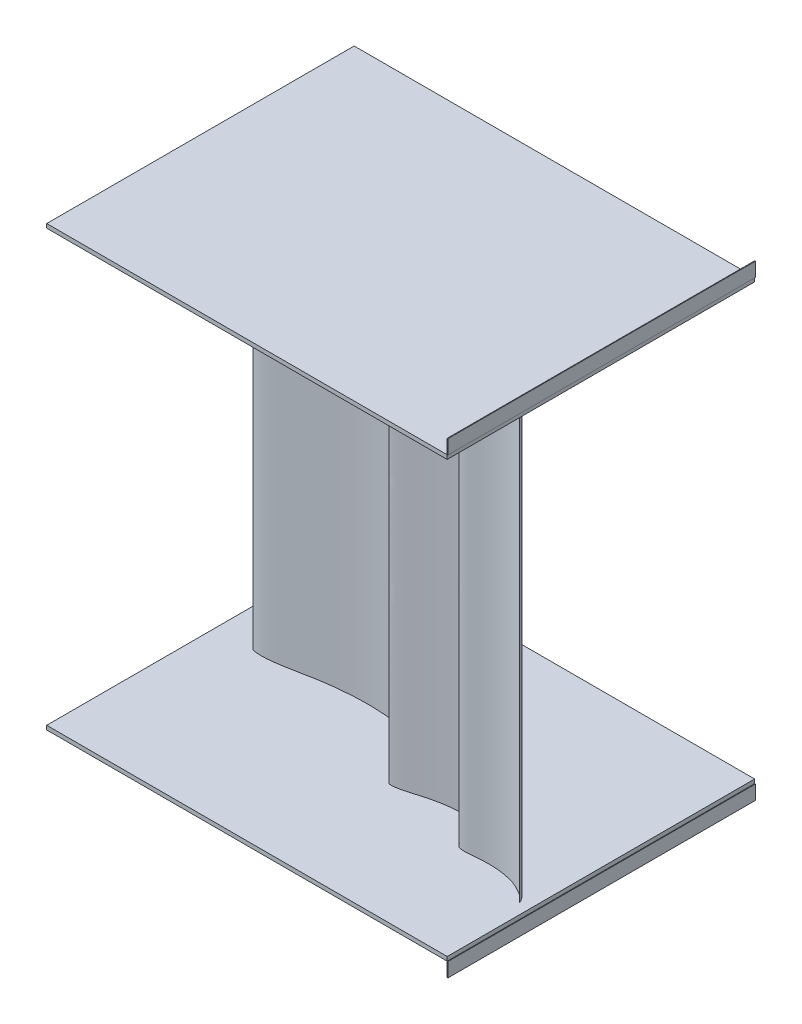
SolidWorks part; units mm, degrees
ref_plane "Front Plane" through (0, 0, 0) normal (0, 0, 1) x (1, 0, 0)
ref_plane "Top Plane" through (0, 0, 0) normal (0, 1, 0) x (1, 0, 0)
ref_plane "Right Plane" through (0, 0, 0) normal (1, 0, 0) x (0, 0, -1)
ref_plane "Plane3" through (0, -431.165, 0) normal (0, 1, 0) x (1, 0, 0)
sketch "Sketch7" plane through (0, -431.165, 0) normal (0, 1, 0) x (1, 0, 0)
  line L3 (2028.85, -589.13) -> (1241.45, -589.13)
  line L6 (1241.45, -1193.65) -> (1241.45, -589.13)
  line L8 (2028.85, -1193.65) -> (2028.85, -589.13)
  line L9 (2028.85, -1193.65) -> (1241.45, -1193.65)
  dimension "D1" = 2028.85
  dimension "D2" = 1193.65
  dimension "D3" = 787.4
  dimension "D4" = 604.52
sketch "Sketch8" plane through (0, 0, 0) normal (0, 1, 0) x (1, 0, 0)
  line L0 (1896.0126, -962.7836) -> (1676.2236, -953.149) construction
  line L1 (1314.0753, -855) -> (1734.7302, -915.6173) construction
  line L2 (1734.7302, -915.6173) -> (1676.2236, -953.149) construction
  line L4 (1314.0753, -855) -> (1319.04, -824.8801) construction
  line L5 (2008.9265, -1031.5984) -> (1853.6118, -993.1619) construction
  line L6 (1734.7302, -915.6173) -> (2013.3954, -915.6173) construction
  line L7 (1853.6118, -993.1619) -> (1896.0126, -962.7836) construction
  line L8 (1896.0126, -962.7836) -> (2113.872, -962.7836) construction
  line L9 (1896.0126, -962.7836) -> (1611.1884, -962.7836) construction
  line L10 (2008.9265, -1031.5984) -> (1908.4474, -1031.5984) construction
  line L16 (2028.85, -589.13) -> (1241.45, -589.13)
  line L17 (1241.45, -589.13) -> (1241.45, -1193.65)
  line L18 (1241.45, -1193.65) -> (2028.85, -1193.65)
  line L19 (2028.85, -1193.65) -> (2028.85, -589.13)
  line L20 (2028.85, -589.13) -> (1241.45, -589.13)
  line L21 (1241.45, -589.13) -> (1241.45, -1193.65)
  line L22 (1241.45, -1193.65) -> (2028.85, -1193.65)
  line L23 (2028.85, -1193.65) -> (2028.85, -589.13)
  spline S2 degree 3 poles (1896.0126, -962.7836) (1895.4061, -961.9813) (1894.5256, -960.8164) (1893.0202, -959.4736) (1891.9514, -958.5728) (1890.9835, -957.615) (1889.9301, -956.8753) (1888.8272, -956.0613) (1887.5489, -955.2375) (1886.2825, -954.2949) (1884.7233, -953.5914) (1883.2352, -952.6696) (1881.6303, -951.8822) (1879.9731, -951.0584) (1878.2946, -950.3229) (1876.6403, -949.5478) (1875.0645, -948.8012) (1873.4398, -948.068) (1871.755, -947.3306) (1870.0069, -946.5947) (1868.2088, -945.8326) (1866.3229, -945.0828) (1864.3352, -944.3316) (1862.2467, -943.5757) (1860.0434, -942.794) (1857.7237, -942.0554) (1855.3392, -941.2719) (1852.8936, -940.5088) (1850.3907, -939.8336) (1847.876, -939.1665) (1845.3582, -938.5369) (1842.8407, -937.9426) (1840.316, -937.4205) (1837.7875, -936.9667) (1835.2619, -936.5383) (1832.7245, -936.2297) (1830.1967, -935.8763) (1827.6616, -935.5985) (1825.123, -935.3793) (1822.5852, -935.1786) (1820.0472, -934.9783) (1817.5053, -934.8632) (1814.9635, -934.7367) (1812.4197, -934.6891) (1809.8765, -934.575) (1807.3296, -934.5687) (1804.781, -934.5931) (1802.2315, -934.6374) (1799.6815, -934.7163) (1797.1308, -934.8095) (1794.5762, -934.889) (1792.0237, -935.0622) (1789.4686, -935.2296) (1786.9096, -935.3927) (1784.3549, -935.6457) (1781.7956, -935.8847) (1779.2318, -936.1302) (1776.6771, -936.484) (1774.1105, -936.7763) (1771.5498, -937.1309) (1768.9836, -937.481) (1766.419, -937.8808) (1763.8523, -938.3091) (1761.2836, -938.7586) (1758.7157, -939.2375) (1756.146, -939.7242) (1753.5903, -940.214) (1751.0656, -940.7832) (1748.5702, -941.3218) (1746.1409, -941.8827) (1743.7872, -942.4259) (1741.5193, -942.9937) (1739.308, -943.5593) (1737.14, -944.1433) (1735.0148, -944.7332) (1732.9199, -945.2861) (1730.891, -945.8607) (1728.9113, -946.4673) (1726.9362, -947.0251) (1724.9914, -947.6136) (1723.0656, -948.2015) (1721.1627, -948.7848) (1719.2274, -949.3326) (1717.2882, -949.9347) (1715.314, -950.5014) (1713.3524, -951.1023) (1711.3803, -951.666) (1709.3957, -952.2526) (1707.3662, -952.8277) (1705.2799, -953.413) (1703.1128, -953.991) (1700.8596, -954.5335) (1698.515, -955.0979) (1696.0607, -955.6034) (1693.534, -956.1045) (1690.9669, -956.5434) (1688.4055, -956.9069) (1685.8421, -957.1294) (1683.2939, -957.2548) (1680.7218, -957.2613) (1678.7711, -957.0514) (1677.1971, -956.861) (1676.6577, -955.9944) (1676.134, -954.8182) (1676.1872, -953.8284) (1676.2236, -953.149) knots 0 0 0 0 0.01297 0.01883 0.026053 0.031073 0.036412 0.042675 0.048819 0.056099 0.063029 0.070869 0.078731 0.08615 0.094825 0.102443 0.109796 0.117394 0.125513 0.133599 0.141944 0.150791 0.159864 0.169447 0.179539 0.190121 0.200953 0.212027 0.223275 0.234503 0.245702 0.256866 0.267981 0.279066 0.290116 0.301131 0.312145 0.323151 0.334135 0.345124 0.356102 0.367084 0.378056 0.38904 0.400013 0.411002 0.421999 0.433003 0.444005 0.455021 0.46604 0.477082 0.48813 0.499184 0.510268 0.521355 0.532455 0.543599 0.554732 0.565889 0.577057 0.588256 0.599481 0.610738 0.622009 0.63329 0.644591 0.655686 0.666786 0.677634 0.687956 0.698051 0.707893 0.717499 0.727111 0.736441 0.745542 0.754403 0.76324 0.772104 0.780702 0.789303 0.797863 0.806734 0.815583 0.824447 0.833287 0.84213 0.851233 0.860589 0.870175 0.880262 0.890586 0.901386 0.912692 0.923927 0.93509 0.94617 0.957198 0.968178 0.979173 0.983282 0.9875 0.991419 1 1 1 1
  spline S3 degree 3 poles (1676.2236, -953.149) (1676.2485, -952.8231) (1676.2986, -952.1665) (1676.5132, -951.1878) (1676.8292, -950.2088) (1677.2564, -949.2276) (1677.7911, -948.2415) (1678.4334, -947.2483) (1679.1823, -946.2459) (1680.0373, -945.2329) (1680.9976, -944.2083) (1682.0622, -943.1717) (1683.2302, -942.1233) (1684.5005, -941.0638) (1685.872, -939.9946) (1687.3432, -938.9176) (1688.9126, -937.8352) (1690.5788, -936.7502) (1692.34, -935.666) (1694.1944, -934.5863) (1696.1401, -933.5149) (1698.175, -932.4562) (1700.297, -931.4143) (1703.2784, -930.0356) (1707.2082, -928.3836) (1712.1762, -926.5606) (1716.5172, -925.1906) (1721.0697, -923.9197) (1724.8413, -923.002) (1729.7024, -921.9798) (1734.7377, -921.0822) (1740.9363, -920.2154) (1746.2195, -919.6563) (1750.5259, -919.2953) (1753.8079, -919.0649) (1757.1216, -918.8736) (1760.4639, -918.719) (1763.8317, -918.5983) (1767.2218, -918.5092) (1770.6309, -918.4493) (1774.0558, -918.4165) (1777.4932, -918.4091) (1782.0918, -918.4313) (1786.6958, -918.4996) (1791.3004, -918.6125) (1794.7496, -918.7218) (1798.1912, -918.8506) (1801.6218, -919.023) (1805.0338, -919.3126) (1808.4245, -919.694) (1811.7906, -920.1649) (1815.1292, -920.7164) (1818.4374, -921.3408) (1821.7122, -922.0304) (1824.9509, -922.7775) (1828.1505, -923.5751) (1831.3081, -924.4169) (1834.4209, -925.297) (1837.486, -926.2109) (1840.5007, -927.1546) (1843.4619, -928.1252) (1846.3668, -929.1208) (1849.2127, -930.1403) (1851.9966, -931.1834) (1854.7157, -932.2504) (1857.3673, -933.3421) (1859.9487, -934.4596) (1862.4572, -935.6041) (1864.8901, -936.7767) (1867.2449, -937.9783) (1869.5193, -939.2092) (1871.7109, -940.4689) (1873.8174, -941.7562) (1875.8368, -943.0689) (1877.7671, -944.4035) (1879.6066, -945.7556) (1881.3535, -947.1194) (1883.0064, -948.4879) (1884.5639, -949.853) (1886.025, -951.2055) (1887.7972, -952.9341) (1889.7588, -954.9907) (1892.0165, -957.5704) (1893.7821, -959.7686) (1894.979, -961.3595) (1895.5192, -962.0976) (1895.7743, -962.4507) (1895.9274, -962.6643) (1895.9955, -962.7597) (1896.0126, -962.7836) knots 0 0 0 0 0.004018 0.008097 0.012294 0.016663 0.021247 0.026085 0.031207 0.036637 0.042391 0.048482 0.054918 0.061703 0.068836 0.076317 0.084139 0.092298 0.100784 0.10959 0.118704 0.128117 0.137818 0.147796 0.16854 0.190267 0.212906 0.224546 0.248433 0.260666 0.285677 0.311368 0.337682 0.351052 0.364552 0.378172 0.391902 0.40573 0.419646 0.433638 0.447693 0.461798 0.475942 0.504289 0.518466 0.532628 0.54676 0.560852 0.574898 0.588895 0.60284 0.616724 0.630537 0.64427 0.657909 0.67144 0.684851 0.698126 0.711251 0.724214 0.737001 0.749602 0.762006 0.774204 0.786189 0.797954 0.809494 0.820805 0.831885 0.84273 0.853339 0.863709 0.873837 0.883718 0.893347 0.902715 0.911811 0.920619 0.929121 0.937297 0.945119 0.959587 0.972264 0.987301 0.994278 0.996765 0.998557 0.999639 1 1 1 1
  spline S6 degree 3 poles (2008.9265, -1031.5984) (2008.6093, -1030.9393) (2008.1489, -1029.9823) (2007.2684, -1028.8088) (2006.6359, -1028.0131) (2006.0833, -1027.1912) (2005.4386, -1026.5125) (2004.7691, -1025.7738) (2003.9761, -1025.0028) (2003.2086, -1024.1489) (2002.198, -1023.4234) (2001.2695, -1022.5525) (2000.2384, -1021.7606) (1999.1752, -1020.9352) (1998.0842, -1020.1698) (1997.016, -1019.3796) (1995.9998, -1018.621) (1994.9468, -1017.8649) (1993.8515, -1017.0972) (1992.7109, -1016.3215) (1991.5384, -1015.5198) (1990.3016, -1014.7144) (1988.9923, -1013.8934) (1987.6119, -1013.0545) (1986.1533, -1012.1807) (1984.6055, -1011.321) (1983.0181, -1010.4199) (1981.3841, -1009.5246) (1979.6966, -1008.6837) (1977.9996, -1007.8469) (1976.2949, -1007.0365) (1974.5854, -1006.2512) (1972.8604, -1005.5163) (1971.1229, -1004.8296) (1969.3838, -1004.1614) (1967.6191, -1003.577) (1965.8677, -1002.962) (1964.1001, -1002.3998) (1962.3217, -1001.8789) (1960.5413, -1001.3714) (1958.7606, -1000.864) (1956.9649, -1000.4169) (1955.1709, -999.9616) (1953.3641, -999.5623) (1951.5673, -999.1157) (1949.7524, -998.7454) (1947.9319, -998.3968) (1946.1078, -998.0622) (1944.2785, -997.7522) (1942.4466, -997.4523) (1940.6138, -997.142) (1938.7692, -996.8989) (1936.9235, -996.6513) (1935.0756, -996.4001) (1933.2179, -996.2135) (1931.3589, -996.0163) (1929.4958, -995.8231) (1927.6236, -995.7084) (1925.7518, -995.5482) (1923.8752, -995.4332) (1921.9953, -995.3142) (1920.1095, -995.231) (1918.2181, -995.1676) (1916.3221, -995.1191) (1914.4226, -995.0918) (1912.5206, -995.0697) (1910.6282, -995.0519) (1908.7464, -995.0951) (1906.89, -995.1207) (1905.0774, -995.1716) (1903.3214, -995.2208) (1901.6229, -995.2999) (1899.9651, -995.3855) (1898.3356, -995.4906) (1896.7357, -995.6059) (1895.1627, -995.6992) (1893.6337, -995.8174) (1892.1351, -995.9656) (1890.6469, -996.0796) (1889.1758, -996.2198) (1887.7183, -996.3624) (1886.278, -996.505) (1884.8195, -996.6175) (1883.3505, -996.7682) (1881.8615, -996.8888) (1880.3767, -997.0354) (1878.8898, -997.1541) (1877.3906, -997.2872) (1875.861, -997.4058) (1874.2896, -997.5235) (1872.6615, -997.6242) (1870.9772, -997.6874) (1869.2246, -997.753) (1867.4022, -997.7609) (1865.5287, -997.7553) (1863.6355, -997.6995) (1861.7572, -997.5908) (1859.8976, -997.3812) (1858.0629, -997.1047) (1856.2282, -996.7399) (1854.8676, -996.3101) (1853.7727, -995.9482) (1853.5126, -995.2529) (1853.3082, -994.3391) (1853.4883, -993.6411) (1853.6118, -993.1619) knots 0 0 0 0 0.01297 0.01883 0.026053 0.031073 0.036412 0.042675 0.048819 0.056099 0.063029 0.070869 0.078731 0.08615 0.094825 0.102443 0.109796 0.117394 0.125513 0.133599 0.141944 0.150791 0.159864 0.169447 0.179539 0.190121 0.200953 0.212027 0.223275 0.234503 0.245702 0.256866 0.267981 0.279066 0.290116 0.301131 0.312145 0.323151 0.334135 0.345124 0.356102 0.367084 0.378056 0.38904 0.400013 0.411002 0.421999 0.433003 0.444005 0.455021 0.46604 0.477082 0.48813 0.499184 0.510268 0.521355 0.532455 0.543599 0.554732 0.565889 0.577057 0.588256 0.599481 0.610738 0.622009 0.63329 0.644591 0.655686 0.666786 0.677634 0.687956 0.698051 0.707893 0.717499 0.727111 0.736441 0.745542 0.754403 0.76324 0.772104 0.780702 0.789303 0.797863 0.806734 0.815583 0.824447 0.833287 0.84213 0.851233 0.860589 0.870175 0.880262 0.890586 0.901386 0.912692 0.923927 0.93509 0.94617 0.957198 0.968178 0.979173 0.983282 0.9875 0.991419 1 1 1 1
  spline S7 degree 3 poles (1853.6118, -993.1619) (1853.6764, -992.9332) (1853.8064, -992.4722) (1854.1, -991.8053) (1854.4659, -991.1527) (1854.9113, -990.5145) (1855.4342, -989.8883) (1856.0348, -989.2724) (1856.7127, -988.6653) (1857.4678, -988.0659) (1858.2995, -987.4734) (1859.2074, -986.8872) (1860.1908, -986.3075) (1861.2486, -985.7346) (1862.3799, -985.1693) (1863.5835, -984.6127) (1864.8579, -984.0664) (1866.2017, -983.5322) (1867.613, -983.0122) (1869.0902, -982.5087) (1870.6312, -982.0244) (1872.2341, -981.5618) (1873.8966, -981.1238) (1876.2202, -980.569) (1879.2592, -979.9557) (1883.063, -979.3695) (1886.3547, -979.0162) (1889.7829, -978.764) (1892.6037, -978.6514) (1896.2162, -978.6208) (1899.9351, -978.7041) (1904.4789, -978.9764) (1908.3258, -979.3366) (1911.4479, -979.6978) (1913.8208, -980.0048) (1916.2108, -980.3444) (1918.616, -980.7142) (1921.0344, -981.1119) (1923.4641, -981.5353) (1925.9033, -981.9822) (1928.3497, -982.4507) (1930.8015, -982.9391) (1934.0769, -983.6154) (1937.3495, -984.3254) (1940.6161, -985.0673) (1943.0596, -985.6405) (1945.4947, -986.2267) (1947.9158, -986.8423) (1950.3068, -987.5389) (1952.6694, -988.2978) (1955.0016, -989.117) (1957.3027, -989.9896) (1959.5716, -990.91) (1961.8073, -991.8719) (1964.009, -992.8697) (1966.1756, -993.898) (1968.3059, -994.9516) (1970.3988, -996.0262) (1972.4528, -997.118) (1974.4665, -998.2238) (1976.4383, -999.3411) (1978.3664, -1000.4681) (1980.2489, -1001.6037) (1982.0839, -1002.7472) (1983.8693, -1003.8985) (1985.603, -1005.0576) (1987.2828, -1006.2251) (1988.9069, -1007.4014) (1990.473, -1008.5868) (1991.9793, -1009.7817) (1993.424, -1010.9859) (1994.8056, -1012.1988) (1996.1225, -1013.4192) (1997.3737, -1014.6451) (1998.5583, -1015.8738) (1999.6755, -1017.102) (2000.7251, -1018.3252) (2001.707, -1019.5383) (2002.6214, -1020.7352) (2003.4687, -1021.9093) (2004.484, -1023.3963) (2005.5871, -1025.1443) (2006.8262, -1027.3078) (2007.7693, -1029.1285) (2008.3941, -1030.4347) (2008.6732, -1031.0385) (2008.8044, -1031.3268) (2008.8829, -1031.5011) (2008.9178, -1031.5789) (2008.9265, -1031.5984) knots 0 0 0 0 0.004018 0.008097 0.012294 0.016663 0.021247 0.026085 0.031207 0.036637 0.042391 0.048482 0.054918 0.061703 0.068836 0.076317 0.084139 0.092298 0.100784 0.10959 0.118704 0.128117 0.137818 0.147796 0.16854 0.190267 0.212906 0.224546 0.248433 0.260666 0.285677 0.311368 0.337682 0.351052 0.364552 0.378172 0.391902 0.40573 0.419646 0.433638 0.447693 0.461798 0.475942 0.504289 0.518466 0.532628 0.54676 0.560852 0.574898 0.588895 0.60284 0.616724 0.630537 0.64427 0.657909 0.67144 0.684851 0.698126 0.711251 0.724214 0.737001 0.749602 0.762006 0.774204 0.786189 0.797954 0.809494 0.820805 0.831885 0.84273 0.853339 0.863709 0.873837 0.883718 0.893347 0.902715 0.911811 0.920619 0.929121 0.937297 0.945119 0.959587 0.972264 0.987301 0.994278 0.996765 0.998557 0.999639 1 1 1 1
  spline S8 degree 3 poles (1314.0753, -855) (1314.0825, -855.1181) (1314.1612, -856.3968) (1313.5566, -858.3073) (1314.3777, -860.552) (1315.2322, -862.3223) (1318.2275, -862.9894) (1321.9335, -863.7667) (1326.8802, -864.2468) (1331.8023, -864.4937) (1336.7727, -864.5571) (1341.766, -864.3489) (1346.7848, -863.9968) (1351.738, -863.5175) (1356.5527, -863.0158) (1361.1677, -862.3801) (1366.9863, -861.578) (1372.5937, -860.5989) (1378.0135, -859.6304) (1381.941, -858.8828) (1385.8399, -858.177) (1389.7257, -857.3977) (1393.6293, -856.6863) (1397.4724, -855.9004) (1401.2976, -855.218) (1405.0671, -854.4612) (1408.8817, -853.6999) (1412.7329, -852.9411) (1416.6364, -852.2471) (1420.5582, -851.4602) (1424.5685, -850.7443) (1428.7013, -850.0828) (1432.8997, -849.3559) (1437.179, -848.6484) (1441.5381, -847.9848) (1446.0065, -847.3275) (1450.635, -846.7342) (1455.4123, -846.1214) (1460.3124, -845.564) (1465.2747, -844.9534) (1470.2813, -844.5013) (1475.3143, -844.0578) (1480.3421, -843.629) (1485.3662, -843.257) (1490.3822, -842.9254) (1495.3886, -842.6479) (1500.3888, -842.4665) (1505.379, -842.2754) (1510.3688, -842.2049) (1515.3474, -842.0142) (1520.3229, -842.0334) (1525.2884, -842.064) (1530.2478, -842.0671) (1535.1982, -842.2436) (1540.1419, -842.4112) (1545.0817, -842.5672) (1550.0077, -842.9036) (1554.9287, -843.213) (1559.8457, -843.5498) (1564.7551, -843.9529) (1569.6589, -844.3941) (1574.5537, -844.894) (1579.4206, -845.6004) (1584.3015, -846.1793) (1589.1634, -846.9092) (1594.0276, -847.6174) (1598.868, -848.4886) (1603.7079, -849.3604) (1608.5458, -850.268) (1613.3659, -851.2875) (1618.1574, -852.451) (1622.976, -853.5301) (1627.7489, -854.8374) (1632.5224, -856.194) (1637.2757, -857.6814) (1642.0012, -859.306) (1646.7207, -860.9984) (1651.4269, -862.7624) (1657.6206, -865.1135) (1663.58, -867.7829) (1669.4152, -870.3019) (1673.5009, -872.2267) (1678.5617, -874.65) (1683.3412, -877.0575) (1687.8401, -879.5165) (1691.0596, -881.266) (1694.157, -883.0061) (1697.1397, -884.7268) (1700.0259, -886.4637) (1703.0576, -888.2705) (1706.1432, -890.0058) (1709.1711, -891.9069) (1712.1054, -893.7279) (1714.7894, -895.7848) (1717.6519, -897.4358) (1719.9057, -899.4904) (1722.2052, -901.3189) (1724.1695, -903.0948) (1726.0527, -904.7185) (1727.7299, -906.745) (1729.6118, -908.6814) (1732.2486, -911.5508) (1733.718, -913.9588) (1734.7302, -915.6173) knots 0 0 0 0 0.000793 0.008585 0.012504 0.016722 0.020831 0.031826 0.042806 0.053834 0.064914 0.076077 0.087312 0.098618 0.109417 0.119742 0.129829 0.14877 0.157874 0.166717 0.175556 0.184421 0.19327 0.20214 0.210701 0.219301 0.227899 0.236764 0.2456 0.254461 0.263562 0.272892 0.282504 0.29211 0.301952 0.312047 0.322369 0.333217 0.344317 0.355411 0.366713 0.377994 0.389264 0.400521 0.411747 0.422945 0.434114 0.44527 0.456404 0.467547 0.478647 0.489735 0.500818 0.511872 0.52292 0.533962 0.544981 0.555997 0.566999 0.578002 0.589 0.599989 0.610962 0.621945 0.632918 0.6439 0.654877 0.665866 0.67685 0.687856 0.69887 0.709885 0.720935 0.73202 0.743135 0.754299 0.765498 0.776726 0.787974 0.80988 0.820462 0.830554 0.840136 0.858057 0.866402 0.874487 0.882606 0.890205 0.897557 0.905175 0.913851 0.921269 0.929131 0.936971 0.943902 0.951181 0.957325 0.963588 0.968927 0.973947 0.98117 0.98703 1 1 1 1
  spline S9 degree 3 poles (1734.7302, -915.6173) (1734.0423, -913.9615) (1732.9859, -911.4188) (1731.1115, -908.1687) (1729.209, -905.744) (1727.2219, -903.2786) (1724.865, -901.1935) (1722.6538, -899.0731) (1720.2391, -897.1403) (1717.7532, -895.1235) (1715.3016, -893.1772) (1713.008, -891.4139) (1710.8413, -889.8239) (1708.6843, -888.1588) (1706.2487, -886.5921) (1703.7846, -884.8639) (1701.214, -883.1783) (1698.5834, -881.3744) (1695.8391, -879.6078) (1693.0863, -877.8922) (1690.3533, -876.1731) (1687.5429, -874.5168) (1683.7591, -872.2114) (1679.8686, -869.9422) (1675.8725, -867.6393) (1672.6849, -865.9084) (1669.4107, -864.1055) (1666.0245, -862.3485) (1662.6533, -860.503) (1659.1356, -858.7781) (1655.5576, -856.9329) (1651.7998, -855.0951) (1647.944, -853.2097) (1643.9554, -851.3507) (1639.8056, -849.4843) (1635.5555, -847.5652) (1631.1974, -845.609) (1626.7381, -843.7067) (1622.206, -841.7932) (1617.626, -839.8183) (1612.9397, -838.0271) (1608.2517, -836.1687) (1603.5497, -834.3688) (1597.2471, -832.0939) (1590.9871, -829.7334) (1584.6817, -827.5313) (1579.9301, -826.0059) (1575.1827, -824.4949) (1570.4268, -823.008) (1564.1436, -820.8839) (1557.7603, -819.1052) (1551.4106, -817.2623) (1546.6301, -815.9735) (1541.8339, -814.7692) (1537.0487, -813.5375) (1532.2542, -812.359) (1527.4587, -811.1976) (1522.6434, -810.1417) (1517.8241, -809.1248) (1513.0045, -808.123) (1508.1671, -807.225) (1503.3311, -806.3257) (1498.4796, -805.5287) (1493.6099, -804.8543) (1488.7453, -804.142) (1483.8629, -803.5592) (1478.9785, -802.9759) (1474.0766, -802.5434) (1469.177, -802.0637) (1464.2669, -801.671) (1459.3489, -801.333) (1454.4211, -801.0406) (1449.482, -800.8387) (1444.5322, -800.7092) (1439.572, -800.654) (1434.6008, -800.6582) (1429.6224, -800.7796) (1424.6263, -800.8521) (1419.6257, -801.182) (1414.6019, -801.4878) (1409.5683, -801.9385) (1404.5993, -802.4753) (1399.8199, -803.0943) (1395.3864, -803.731) (1391.2954, -804.4001) (1387.492, -805.1985) (1383.8529, -805.937) (1379.3955, -807.0558) (1375.1617, -808.1701) (1371.1779, -809.3546) (1368.3607, -810.256) (1365.6681, -811.2186) (1363.0442, -812.1767) (1360.4883, -813.1339) (1358.011, -814.1316) (1355.6065, -815.1809) (1353.293, -816.3002) (1351.0295, -817.3912) (1348.8946, -818.4942) (1346.9493, -819.5877) (1345.0302, -820.5889) (1343.1845, -821.6846) (1341.4102, -822.7907) (1339.738, -823.8699) (1338.2047, -825.0091) (1336.5642, -826.058) (1335.0246, -827.2714) (1333.4063, -828.3977) (1331.9835, -829.6592) (1330.5579, -830.8332) (1329.2128, -832.0628) (1327.8187, -833.3268) (1326.4907, -834.6657) (1324.8288, -836.4161) (1323.3181, -838.2033) (1321.7939, -839.8966) (1320.8084, -841.1927) (1319.8298, -842.4845) (1318.9582, -843.904) (1318.021, -845.3658) (1317.1932, -847.0077) (1316.2454, -848.6318) (1315.4123, -850.3821) (1314.5929, -852.1048) (1314.3596, -853.7073) (1314.1505, -854.6578) (1314.0753, -855) knots 0 0 0 0 0.011426 0.017546 0.023852 0.031067 0.037693 0.043881 0.050605 0.057403 0.064303 0.070569 0.075854 0.081445 0.087939 0.094312 0.100641 0.107544 0.114656 0.121456 0.128233 0.135247 0.142261 0.156493 0.163973 0.171676 0.179627 0.187813 0.196007 0.204136 0.212797 0.221684 0.230817 0.240172 0.249749 0.259839 0.269916 0.280217 0.290759 0.301294 0.312025 0.322753 0.33346 0.344135 0.36549 0.37613 0.38673 0.397318 0.407907 0.418511 0.439617 0.450159 0.46068 0.471194 0.481699 0.492196 0.502685 0.513169 0.523637 0.5341 0.544565 0.555017 0.565473 0.575919 0.586373 0.59683 0.607279 0.617746 0.628214 0.638679 0.649162 0.659655 0.670164 0.68069 0.691235 0.701802 0.712395 0.722998 0.733664 0.744352 0.7551 0.765894 0.776228 0.785837 0.794461 0.802661 0.810622 0.818143 0.831966 0.838544 0.84465 0.85083 0.856781 0.862467 0.868237 0.873813 0.879196 0.884627 0.88984 0.894519 0.898859 0.903643 0.908203 0.912197 0.916332 0.920381 0.924604 0.928828 0.932943 0.936719 0.940607 0.944563 0.94872 0.952631 0.959956 0.963643 0.967152 0.970338 0.973973 0.977769 0.981405 0.985692 0.989749 0.993788 0.997763 1 1 1 1
  dimension "D1" = 144.38
  dimension "D2" = 220
  dimension "D3" = 52.16
  dimension "D4" = 13.9
  dimension "D5" = 160
  dimension "D6" = 147.32
  dimension "D7" = 2.51
  dimension "D8" = 69.51
  dimension "D9" = 0
extrude "Boss-Extrude10" add sketch "Sketch7" along normal blind 8
sketch "Sketch10" plane through (0, -431.165, 0) normal (0, 1, 0) x (1, 0, 0)
  line L0 (2028.85, -1193.65) -> (2028.85, -589.13)
extrude "Extrude-Thin1" add sketch "Sketch10" against normal blind 28 thin thin type one direction wall 1.27
sketch3d "3DSketch1"
  spline S6 degree 3 poles (942.5392, 188.4893, 77.3735) (942.832, 206.2376, 89.8009) (943.1316, 224.3948, 102.5148) (943.4379, 242.961, 115.515) (943.4592, 244.157, 116.4183) (943.4737, 244.9459, 117.0306) (943.481, 245.3372, 117.3406) (943.8045, 262.6762, 131.0729) (944.2671, 272.861, 150.7043) (944.7874, 274.1067, 172.7831) (944.7986, 274.1335, 173.2594) (944.8211, 274.1783, 174.2126) (944.8548, 274.2277, 175.644) (947.8227, 274.2277, 301.5982) (950.7912, 274.2277, 427.5757) (953.7602, 274.2277, 553.5766) (953.7955, 274.2114, 555.0778) (953.8191, 274.1966, 556.0786) (953.8309, 274.1877, 556.5789) (954.4859, 273.6948, 584.3754) (955.1304, 268.6853, 611.729) (955.7473, 259.2854, 637.9089) (955.771, 258.9244, 638.9142) (955.8183, 258.1899, 640.9201) (955.889, 257.0625, 643.9205) (958.5742, 211.2068, 757.88) (961.2452, 165.5959, 871.2312) (963.9018, 120.2297, 983.9742) (963.9285, 119.7336, 985.1083) (963.9462, 119.3949, 985.8605) (963.9551, 119.2225, 986.2351) (964.5802, 107.0139, 1012.7657) (964.9651, 82.8061, 1029.1002) (964.998, 53.6375, 1030.4941) (964.9984, 53.2336, 1030.5134) (964.9992, 52.4257, 1030.5456) (965, 51.2128, 1030.581) (965, 17.0709, 1030.581) (965, -17.0709, 1030.581) (965, -51.2128, 1030.581) (964.9992, -52.4257, 1030.5456) (964.9984, -53.2336, 1030.5134) (964.998, -53.6375, 1030.4941) (964.9651, -82.8061, 1029.1002) (964.5802, -107.0139, 1012.7657) (963.9551, -119.2225, 986.2351) (963.9462, -119.3949, 985.8605) (963.9285, -119.7336, 985.1083) (963.9018, -120.2297, 983.9742) (961.2452, -165.5959, 871.2312) (958.5742, -211.2068, 757.88) (955.889, -257.0625, 643.9205) (955.8183, -258.1899, 640.9201) (955.771, -258.9244, 638.9142) (955.7473, -259.2854, 637.9089) (955.1304, -268.6853, 611.729) (954.4859, -273.6948, 584.3754) (953.8309, -274.1877, 556.5789) (953.8191, -274.1966, 556.0786) (953.7955, -274.2114, 555.0778) (953.7602, -274.2277, 553.5766) (950.7912, -274.2277, 427.5757) (947.8227, -274.2277, 301.5982) (944.8548, -274.2277, 175.644) (944.8211, -274.1783, 174.2126) (944.7986, -274.1335, 173.2594) (944.7874, -274.1067, 172.7831) (944.2627, -272.8505, 150.5184) (943.7972, -262.5143, 130.7622) (943.4738, -244.9486, 117.0348) (943.4614, -244.2771, 116.5101) (943.4372, -242.9166, 115.4831) (943.4026, -240.8209, 114.0165) (943.1017, -222.679, 101.3134) (942.8124, -205.2351, 89.099) (942.5347, -188.4893, 77.3735) knots 0 0 0 0 0.029375 0.030052 0.030729 0.031406 0.031406 0.031406 0.059643 0.059643 0.059643 0.06029 0.060937 0.061584 0.231154 0.231833 0.232512 0.233191 0.233191 0.233191 0.270549 0.270549 0.270549 0.271995 0.273442 0.274888 0.438359 0.438917 0.439476 0.440034 0.440034 0.440034 0.475757 0.475757 0.475757 0.476305 0.476853 0.4774 0.522556 0.523104 0.523651 0.524199 0.524199 0.524199 0.559922 0.559922 0.559922 0.560481 0.561039 0.561598 0.725068 0.726515 0.727961 0.729408 0.729408 0.729408 0.766766 0.766766 0.766766 0.767444 0.768123 0.768802 0.938372 0.939019 0.939667 0.940314 0.940314 0.940314 0.968774 0.968774 0.968774 0.969931 0.971088 0.972245 1 1 1 1 weights 1 1 1 1 1 1 1 0.941603 0.94179 1.000561 1.000561 1.000561 1.000561 1.000561 1.000561 1.000561 1.000561 1.000561 1.000561 0.991124 0.990575 0.998913 0.998913 0.998913 0.998913 0.998913 0.998913 0.998913 0.998913 0.998913 0.998913 0.902209 0.902299 0.999183 0.999183 0.999183 0.999183 0.999183 0.999183 0.999183 0.999183 0.999183 0.999183 0.902299 0.902209 0.998913 0.998913 0.998913 0.998913 0.998913 0.998913 0.998913 0.998913 0.998913 0.998913 0.990575 0.991124 1.000561 1.000561 1.000561 1.000561 1.000561 1.000561 1.000561 1.000561 1.000561 1.000561 0.941325 0.941604 1.001399 1.001399 1.001399 1.001399 1.001399 1.001399 1.001399
sketch "Sketch12" plane through (0, 0, 0) normal (0, 1, 0) x (1, 0, 0)
  line L0 (1199.061, -595.1441) -> (1199.061, -643.2623) construction
  line L1 (967.5392, -77.3735) -> (967.5392, -1304.4116) construction
  line L2 (1040, -595.1441) -> (1238.0413, -595.1441)
  line L3 (1040, -595.1441) -> (1238.0413, -595.1441) construction
  line L4 (967.5392, -77.3735) -> (1085.2537, -1036.0813)
  line L5 (1077.558, -920.178) -> (1229.1053, -920.178) construction
  line L6 (1199.061, -595.1441) -> (1078.6209, -877.964)
  line L8 (990, -1043.281) -> (933.768, -1043.281) construction
  line L9 (1223.2734, -573.2347) -> (1261.1883, -569.4837) construction
  line L11 (-11.7203, -883.6813) -> (49988.2797, -883.6813) construction
  line L12 (990, -1030.581) -> (1083.706, -1023.4759)
  line L13 (1079.3229, -883.6813) -> (1211.0114, -574.4478)
  line L14 (990, -1043.281) -> (1085.2537, -1036.0813)
  line L15 (990, -1017.881) -> (1082.161, -1010.8931)
  line L16 (1083.706, -1023.4759) -> (1120.5127, -1020.6851)
  line L17 (1096.3696, -1022.5157) -> (979.7131, -72.4247)
  line L19 (1071.0423, -1024.4361) -> (955.1011, -80.1702)
  line L20 (1075.5317, -852.8043) -> (1185.2574, -595.1441)
  line L21 (1078.6209, -877.964) -> (1068.6999, -901.2609)
  line L23 (1081.8109, -877.839) -> (1101.7146, -831.1005)
  circle A1 centre (990, -1030.581) radius 12.7
  circle A4 centre (1083.706, -1023.4759) radius 12.7
  ellipse E1 centre (1242.9353, -674.1196) end of major axis (1245.3483, -674.1196) minor radius 2.3721
  ellipse E3 centre (1077.558, -920.178) end of major axis (1079.971, -920.178) minor radius 2.3721
  point P4 (967.5392, -77.3735)
  point P7 (1083.706, -1023.4759)
  point P21 (1199.061, -595.1441)
  point P23 (1082.161, -1010.8931)
  point P27 (1091.7628, -854.4698)
  point P29 (1096.3696, -1022.5157)
  point P30 (1071.0423, -1024.4361)
  point P38 (1079.3229, -883.6813)
  point P48 (1078.6209, -877.964)
  dimension "D3" = 25.4
  dimension "D5" = 965.9075
  dimension "D6" = 25.4
  dimension "D1" = 0
  dimension "D2" = 7
  dimension "D4" = 152.4
  dimension "D7" = 31.75
  dimension "D9" = 25.4
  dimension "D11" = 12.7
  dimension "D12" = 25.4
extrude "Boss-Extrude8" add sketch "Sketch8" against normal up to surface (423.165 mm away) contours S3 S2 | S6 S7 | S8 S9 region at (1762.7344, 0, 934.3911) up to face at (1635.15, -423.165, 891.39)
mirror "Mirror1" about plane through (0, 0, 0) normal (0, 1, 0) of bodies 141 142 143 144 138 140
combine bodies "Combine1" operation type add bodies to combine 148 144
combine bodies "Combine2" operation type add bodies to combine 147 143
combine bodies "Combine3" operation type add bodies to combine 149 138
